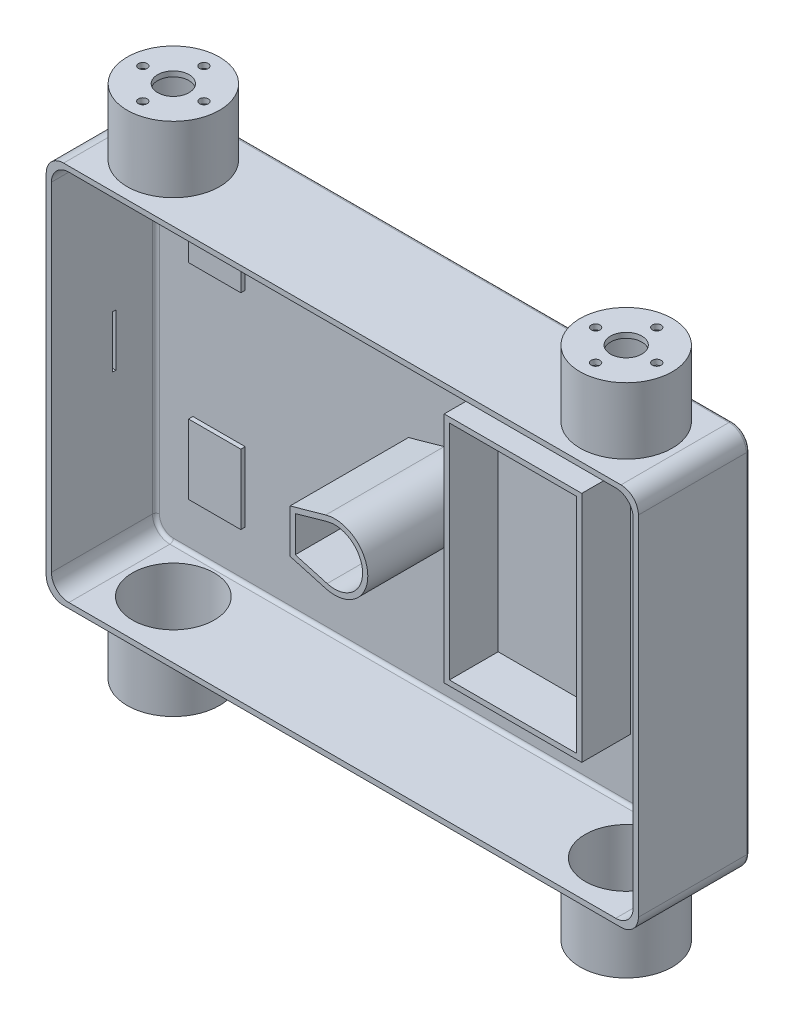
SolidWorks part; units mm, degrees
other "Markup1"
sketch "Sketch12" plane through (200, -100, 73) normal (0.8707, -0.1395, 0.4717) x (0.0835, 0.9869, 0.1379)
ref_plane "Front Plane" through (0, 0, 0) normal (0, 0, 1) x (1, 0, 0)
ref_plane "Top Plane" through (0, 0, 0) normal (0, 1, 0) x (1, 0, 0)
ref_plane "Right Plane" through (0, 0, 0) normal (1, 0, 0) x (0, 0, -1)
sketch "Sketch2" plane through (0, 0, 0) normal (0, 0, 1) x (1, 0, 0)
  line L1 (-170, -110) -> (170, -110)
  line L2 (-170, -110) -> (-170, 110)
  line L3 (-170, 110) -> (170, 110)
  line L4 (170, -110) -> (170, 110)
  line L5 (-170, -110) -> (170, 110) construction
  line L6 (-170, 110) -> (170, -110) construction
  point P0 (0, 0)
  dimension "D1" = 340
  dimension "D2" = 220
extrude "Boss-Extrude1" add sketch "Sketch2" along normal blind 4 contours L2 L1 L4 L3
sketch "Sketch3" plane through (0, 0, 4) normal (0, 0, 1) x (1, 0, 0)
  line L0 (-167, 107) -> (-167, -107)
  line L1 (-167, -107) -> (167, -107)
  line L2 (167, -107) -> (167, 107)
  line L3 (167, 107) -> (-167, 107)
  line L4 (170, 110) -> (-170, 110)
  line L5 (-170, 110) -> (-170, -110)
  line L6 (-170, -110) -> (170, -110)
  line L7 (170, -110) -> (170, 110)
  line L8 (170, 110) -> (-170, 110)
  line L9 (-170, 110) -> (-170, -110)
  line L10 (-170, -110) -> (170, -110)
  line L11 (170, -110) -> (170, 110)
  dimension "D1" = 0
  dimension "D2" = 3
extrude "Boss-Extrude2" add sketch "Sketch3" along normal blind 60
fillet "Fillet1" radius 10 8 edges at (-170, 110, 32) (170, 110, 32) (170, -110, 32) (-170, -110, 32) (167, 107, 34) (167, -107, 34) (-167, 107, 34) (-167, -107, 34)
fillet "Fillet2" radius 2 8 edges at (-167.0711, 107.0711, 0) (-170, 0, 0) (-167.0711, -107.0711, 0) (0, -110, 0) (167.0711, -107.0711, 0) (170, 0, 0) (167.0711, 107.0711, 0) (0, 110, 0)
fillet "Fillet3" radius 2 8 edges at (164.0711, 104.0711, 4) (167, 0, 4) (164.0711, -104.0711, 4) (0, -107, 4) (-164.0711, -104.0711, 4) (-167, 0, 4) (-164.0711, 104.0711, 4) (0, 107, 4)
sketch "Sketch5" plane through (0, 107, 0) normal (0, -1, 0) x (1, 0, 0)
  line L0 (-157, 18) -> (157, 18) construction
  line L1 (-157, 64) -> (-157, 6) construction
  line L2 (157, 6) -> (157, 64) construction
  line L3 (-157, 6) -> (157, 6) construction
  circle A0 centre (-142, 18) radius 10
  circle A1 centre (142, 18) radius 10
  dimension "D2" = 20
  dimension "D3" = 20
  dimension "D5" = 15
  dimension "D1" = 12
  dimension "D4" = 15
extrude "Cut-Extrude1" cut sketch "Sketch5" against normal through all both and the other way through all
sketch "Sketch6" plane through (0, 0, 0) normal (0, 1, 0) x (1, 0, 0)
  line L0 (-170, -17) -> (-175.2094, -46.5442)
  line L1 (-170, -2) -> (-170, -64) construction
  line L2 (-175.2094, -46.5442) -> (-170, -46.5442)
  line L3 (-170, -46.5442) -> (-170, -17)
  dimension "D1" = 30
  dimension "D2" = 15
  dimension "D3" = 10
extrude "Boss-Extrude3" add sketch "Sketch6" along normal mid plane 30
sketch "Sketch7" plane through (-167, 0, 0) normal (1, 0, 0) x (0, 0, -1)
  line L0 (-2, 100) -> (-2, -100) construction
  line L1 (-27, 15) -> (-29, 15)
  line L2 (-27, 15) -> (-27, -15)
  line L3 (-27, -15) -> (-29, -15)
  line L4 (-29, 15) -> (-29, -15)
  line L6 (-63.9373, 0) -> (0, 0) construction
  dimension "D1" = 25
  dimension "D2" = 2
  dimension "D3" = 30
  dimension "D4" = 63.9373
extrude "Cut-Extrude3" cut sketch "Sketch7" against normal blind 30
other "DeleteFace1" face at (132, -107, 18) and patch yes
other "DeleteFace2" face at (-152, -107, 18) face at (-132, 107, 18) face at (152, 107, 18) and patch yes
sketch "Sketch11" plane through (0, -107, 0) normal (0, 1, 0) x (1, 0, 0)
  line L0 (157, -6) -> (-157, -6) construction
  line L1 (157, -64) -> (157, -6) construction
  circle A0 centre (130, -31) radius 23.5
  dimension "D1" = 47
  dimension "D2" = 25
  dimension "D3" = 27
extrude "Cut-Extrude6" cut sketch "Sketch11" against normal through all both and the other way through all
sketch "Sketch14" plane through (0, -107, 0) normal (0, 1, 0) x (1, 0, 0)
  line L0 (-157, -6) -> (-157, -64) construction
  line L1 (157, -6) -> (-157, -6) construction
  circle A0 centre (-130, -31) radius 23.5
  dimension "D1" = 47
  dimension "D2" = 27
  dimension "25" = 25
extrude "Cut-Extrude7" cut sketch "Sketch14" against normal through all both and the other way through all
sketch "Sketch15" plane through (0, -110, 0) normal (0, -1, 0) x (1, 0, 0)
  circle A6 centre (-130, 31) radius 26.5
  circle A7 centre (-130, 31) radius 26.5
  circle A8 centre (130, 31) radius 23.5 construction
  circle A9 centre (130, 31) radius 26.5
  circle A10 centre (130, 31) radius 26.5
  circle A11 centre (-130, 31) radius 23.5 construction
  circle A12 centre (130, 31) radius 23.5
  circle A13 centre (-130, 31) radius 23.5
  dimension "D1" = 3
  dimension "D2" = 3
extrude "Boss-Extrude5" add sketch "Sketch15" along normal blind 35
sketch "Sketch16" plane through (0, -145, 0) normal (0, -1, 0) x (1, 0, 0)
  circle A0 centre (-130, 31) radius 26.5 construction
  circle A1 centre (-130, 31) radius 26.5
extrude "Boss-Extrude6" add sketch "Sketch16" along normal blind 3
sketch "Sketch17" plane through (0, -145, 0) normal (0, -1, 0) x (1, 0, 0)
  circle A1 centre (130, 31) radius 26.5
  circle A2 centre (130, 31) radius 26.5
  dimension "D1" = 0
extrude "Boss-Extrude7" add sketch "Sketch17" along normal blind 3 contours A2
sketch "Sketch18" plane through (0, -148, 0) normal (0, -1, 0) x (1, 0, 0)
  circle A0 centre (-130, 31) radius 9
  circle A1 centre (130, 31) radius 9
  dimension "D1" = 18
  dimension "D2" = 18
extrude "Cut-Extrude8" cut sketch "Sketch18" against normal up to next
mirror "Mirror1" about plane through (0, 0, 0) normal (0, 1, 0) of "Boss-Extrude5", "Boss-Extrude6", "Cut-Extrude8", "Boss-Extrude7"
sketch "Sketch20" plane through (0, 145, 0) normal (0, -1, 0) x (1, 0, 0)
  line L0 (-130, 7.5) -> (-130, 54.5) construction
  circle A0 centre (-130, 48.55) radius 2.5
  circle A1 centre (-130, 31) radius 23.5 construction
  circle A2 centre (-130, 31) radius 9 construction
  circle A3 centre (-130, 31) radius 17.55
  circle A4 centre (-112.45, 31) radius 2.5
  circle A5 centre (-130, 13.45) radius 2.5
  circle A6 centre (-147.55, 31) radius 2.5
  point P5 (-130, 31)
  point P20 (-130, 31)
  dimension "D1" = 5
  dimension "D2" = 17.55
  dimension "D3" = 35.1
  dimension "D4" = 4
extrude "Cut-Extrude9" cut sketch "Sketch20" against normal up to next contours A3 L0 A0 | L0 A3 A0 | A0 L0 A3 | L0 A0 A3 | A3 A4 | A3 A4 | A5 L0 A3 | L0 A5 A3 | L0 A3 A5 | A3 L0 A5 | A3 A6 | A3 A6 region at (-131.0849, 145, 12.4217) region at (-128.9151, 145, 12.4217) region at (-131.0357, 145, 14.5425) region at (-128.9643, 145, 14.5425) region at (-148.5783, 145, 31) region at (-146.4575, 145, 31) region at (-131.0357, 145, 47.4575) region at (-128.9643, 145, 47.4575) region at (-113.5425, 145, 31) region at (-111.4217, 145, 31) region at (-131.0849, 145, 49.5783) region at (-128.9151, 145, 49.5783)
mirror "Mirror2" about plane through (0, 0, 0) normal (1, 0, 0) of "Cut-Extrude9"
mirror "Mirror3" about plane through (0, 0, 0) normal (0, 1, 0) of "Mirror2", "Cut-Extrude9"
sketch "Sketch21" plane through (0, 0, 4) normal (0, 0, 1) x (1, 0, 0)
  line L0 (130, 148) -> (132.5, -148) construction
  line L1 (156.5, 148) -> (103.5, 148) construction
  line L2 (157, 105) -> (-157, 105) construction
  line L3 (115.7527, 38.8769) -> (145.7527, 38.8769)
  line L4 (115.7527, 38.8769) -> (115.7527, 78.8769)
  line L5 (115.7527, 78.8769) -> (145.7527, 78.8769)
  line L6 (145.7527, 38.8769) -> (145.7527, 78.8769)
  line L7 (115.7527, 38.8769) -> (145.7527, 78.8769) construction
  line L8 (115.7527, 78.8769) -> (145.7527, 38.8769) construction
  line L9 (55, 0) -> (-55, 0) construction
  line L10 (115.7527, -78.8769) -> (145.7527, -78.8769)
  line L11 (115.7527, -38.8769) -> (115.7527, -78.8769)
  line L12 (115.7527, -38.8769) -> (145.7527, -38.8769)
  line L13 (145.7527, -38.8769) -> (145.7527, -78.8769)
  line L14 (0, -55) -> (0, 55) construction
  line L15 (-115.7527, -38.8769) -> (-145.7527, -38.8769)
  line L16 (-115.7527, -38.8769) -> (-115.7527, -78.8769)
  line L17 (-115.7527, -78.8769) -> (-145.7527, -78.8769)
  line L18 (-145.7527, -38.8769) -> (-145.7527, -78.8769)
  line L19 (-115.7527, 78.8769) -> (-145.7527, 78.8769)
  line L20 (-145.7527, 38.8769) -> (-145.7527, 78.8769)
  line L21 (-115.7527, 38.8769) -> (-145.7527, 38.8769)
  line L22 (-115.7527, 38.8769) -> (-115.7527, 78.8769)
  point P5 (130.7527, 58.8769)
  dimension "D1" = 40
  dimension "D2" = 30
  dimension "D3" = 26.1231
extrude "Boss-Extrude8" add sketch "Sketch21" along normal blind 2.5
extrude "Cut-Extrude19" cut sketch "Sketch34" against normal blind 2
sketch "Sketch34" plane through (16.1908, -13.9668, 4) normal (0, 0, 1) x (1, 0, 0)
  line L16 (86.3092, 73.5013) -> (13.3092, 73.5013)
  line L17 (13.3092, 73.5013) -> (13.3092, -54.2887)
  line L18 (13.3092, -54.2887) -> (86.3092, -54.2887)
  line L19 (86.3092, -54.2887) -> (86.3092, 73.5013)
  line L32 (89.3092, 76.5013) -> (10.3092, 76.5013)
  line L33 (10.3092, 76.5013) -> (10.3092, -57.2887)
  line L34 (10.3092, -57.2887) -> (89.3092, -57.2887)
  line L35 (89.3092, -57.2887) -> (89.3092, 76.5013)
sketch "Sketch35" plane through (0, 0, 2) normal (0, 0, 1) x (1, 0, 0)
  line L4 (105.5, -71.2555) -> (105.5, 62.5345)
  line L5 (105.5, 62.5345) -> (26.5, 62.5345)
  line L6 (26.5, 62.5345) -> (26.5, -71.2555)
  line L7 (26.5, -71.2555) -> (105.5, -71.2555)
  line L8 (105.5, -71.2555) -> (105.5, 62.5345)
  line L9 (105.5, 62.5345) -> (26.5, 62.5345)
  line L10 (26.5, 62.5345) -> (26.5, -71.2555)
  line L11 (26.5, -71.2555) -> (105.5, -71.2555)
  line M5 (102.5, -68.2555) -> (29.5, -68.2555)
  line M6 (29.5, -68.2555) -> (29.5, 59.5345)
  line M7 (29.5, 59.5345) -> (102.5, 59.5345)
  line M8 (102.5, 59.5345) -> (102.5, -68.2555)
  dimension "D1" = 0
extrude "Boss-Extrude9" add sketch "Sketch35" along normal blind 30 contours M5 M8 M7 M6 | L8 L9 L10 L11 region at (66, -4.3605, 2)
extrude "Cut-Extrude20" cut sketch "Sketch36" against normal blind 2
sketch "Sketch36" plane through (16.1908, -13.9668, 4) normal (0, 0, 1) x (1, 0, 0)
  line L7 (-38.1908, 1.4354) -> (-17.6781, -4.3255)
  line L8 (-17.6781, 32.2591) -> (-38.1908, 26.4982)
  line L9 (-38.1908, 26.4982) -> (-38.1908, 1.4354)
  line L13 (-16.867, 29.3708) -> (-35.1908, 24.2246)
  line L14 (-35.1908, 24.2246) -> (-35.1908, 3.7089)
  line L15 (-35.1908, 3.7089) -> (-16.867, -1.4372)
  arc A3 (-17.6781, -4.3255) -> (-17.6781, 32.2591) centre (-12.5408, 13.9668) ccw
  arc A5 (-16.867, -1.4372) -> (-16.867, 29.3708) centre (-12.5408, 13.9668) ccw
sketch "Sketch37" plane through (0, 0, 2) normal (0, 0, 1) x (1, 0, 0)
  line L3 (-22, 12.5314) -> (-22, -12.5314)
  line L4 (-22, -12.5314) -> (-1.4873, -18.2923)
  line L5 (-1.4873, 18.2923) -> (-22, 12.5314)
  line L6 (-22, 12.5314) -> (-22, -12.5314)
  line L7 (-22, -12.5314) -> (-1.4873, -18.2923)
  line L8 (-1.4873, 18.2923) -> (-22, 12.5314)
  line L9 (-19, -10.2578) -> (-0.6762, -15.404)
  line L10 (-0.6762, 15.404) -> (-19, 10.2578)
  line L11 (-19, 10.2578) -> (-19, -10.2578)
  line L12 (-19, -10.2578) -> (-0.6762, -15.404)
  line L13 (-0.6762, 15.404) -> (-19, 10.2578)
  line L14 (-19, 10.2578) -> (-19, -10.2578)
  arc A1 (-1.4873, -18.2923) -> (-1.4873, 18.2923) centre (3.65, 0) ccw
  arc A2 (-1.4873, -18.2923) -> (-1.4873, 18.2923) centre (3.65, 0) ccw
  arc A3 (-0.6762, -15.404) -> (-0.6762, 15.404) centre (3.65, 0) ccw
  arc A4 (-0.6762, -15.404) -> (-0.6762, 15.404) centre (3.65, 0) ccw
  dimension "D1" = 0
  dimension "D2" = 0
extrude "Boss-Extrude10" add sketch "Sketch37" along normal blind 70
extrude "Cut-Extrude21" cut sketch "Sketch38" against normal blind 4
sketch "Sketch38" plane through (16.1908, -13.9668, 0) normal (0, 0, -1) x (-1, 0, 0)
  circle A3 centre (12.5408, 13.9668) radius 13.05
